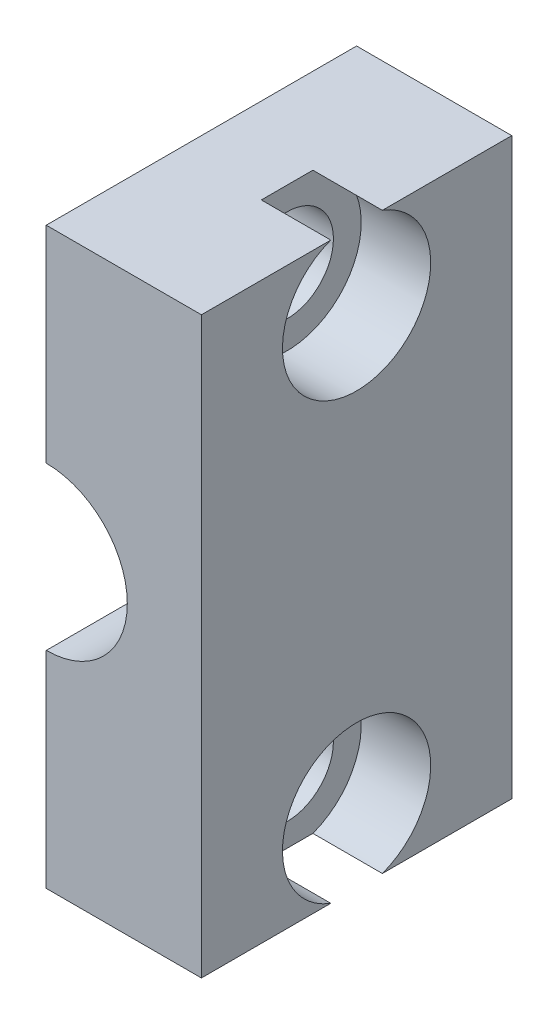
SolidWorks part; units mm, degrees
note: The reader was unsure of these and kept them because the rebuilt part matched: shared geometry of "草图1<4>", "草图1<5>", "草图4<3>".
ref_plane "前视基准面" through (0, 0, 0) normal (0, 0, 1) x (1, 0, 0)
ref_plane "上视基准面" through (0, 0, 0) normal (0, 1, 0) x (1, 0, 0)
ref_plane "右视基准面" through (0, 0, 0) normal (1, 0, 0) x (0, 0, -1)
other "Configuration Table"
sketch "草图1" plane through (0, 0, 0) normal (0, 0, 1) x (1, 0, 0)
  line L5 (0, 6.2) -> (3.35, 6.2)
  line L6 (0, 6.2) -> (0, -6.2)
  line L11 (0, -6.2) -> (3.35, -6.2)
  line L12 (3.35, 6.2) -> (3.35, -6.2)
  circle A0 centre (0, 0) radius 3.2
  dimension "D1" = 6.4
  dimension "D2" = 12.4
  dimension "D3" = 3.35
extrude "凸台-拉伸1" add sketch "草图1" along normal blind 2.7 contours A0 L6 L11 L12 L5
extrude "凸台-拉伸2" add sketch "草图1<4>" against normal blind 2 contours L5 L12 L11 L6
sketch "草图1<4>" plane through (0, 0, 0) normal (0, 0, 1) x (1, 0, 0) same geometry as "草图1"
extrude "凸台-拉伸3" add sketch "草图1<5>" along normal blind 2 from surface at 2.7 contours L5 L12 L11 L6 starting at face at (1.65, 0, 2.7)
sketch "草图1<5>" plane through (0, 0, 0) normal (0, 0, 1) x (1, 0, 0) same geometry as "草图1"
sketch "草图2" plane through (0, 0, 4.7) normal (0, 0, 1) x (1, 0, 0)
  line L0 (0, -6.2) -> (0, 6.2) construction
  circle A0 centre (0, 0) radius 1.75
  dimension "D1" = 3.5
extrude "切除-拉伸1" cut sketch "草图2" against normal through all
sketch "草图4" plane through (3.35, 0, 0) normal (1, 0, 0) x (0, 0, -1)
  line L0 (-1.35, 6.2) -> (-1.35, 4.7) construction
  line L3 (-4.7, 6.2) -> (2, 6.2) construction
  line L4 (-1.35, 4.7) -> (-1.35, -4.7) construction
  line L5 (-1.35, -4.7) -> (-1.35, -6.2) construction
  line L6 (-4.7, -6.2) -> (2, -6.2) construction
  circle A0 centre (-1.35, -4.7) radius 1
  circle A1 centre (-1.35, 4.7) radius 1
  circle A2 centre (-1.35, 4.7) radius 1.6
  circle A3 centre (-1.35, -4.7) radius 1.6
  dimension "D2" = 2
  dimension "D3" = 3.2
  dimension "D1" = 1.5
extrude "切除-拉伸2" cut sketch "草图4" against normal through all contours A1 | A0
extrude "切除-拉伸3" cut sketch "草图4<3>" against normal blind 1.5
sketch "草图4<3>" plane through (3.35, 0, 0) normal (1, 0, 0) x (0, 0, -1) same geometry as "草图4"
